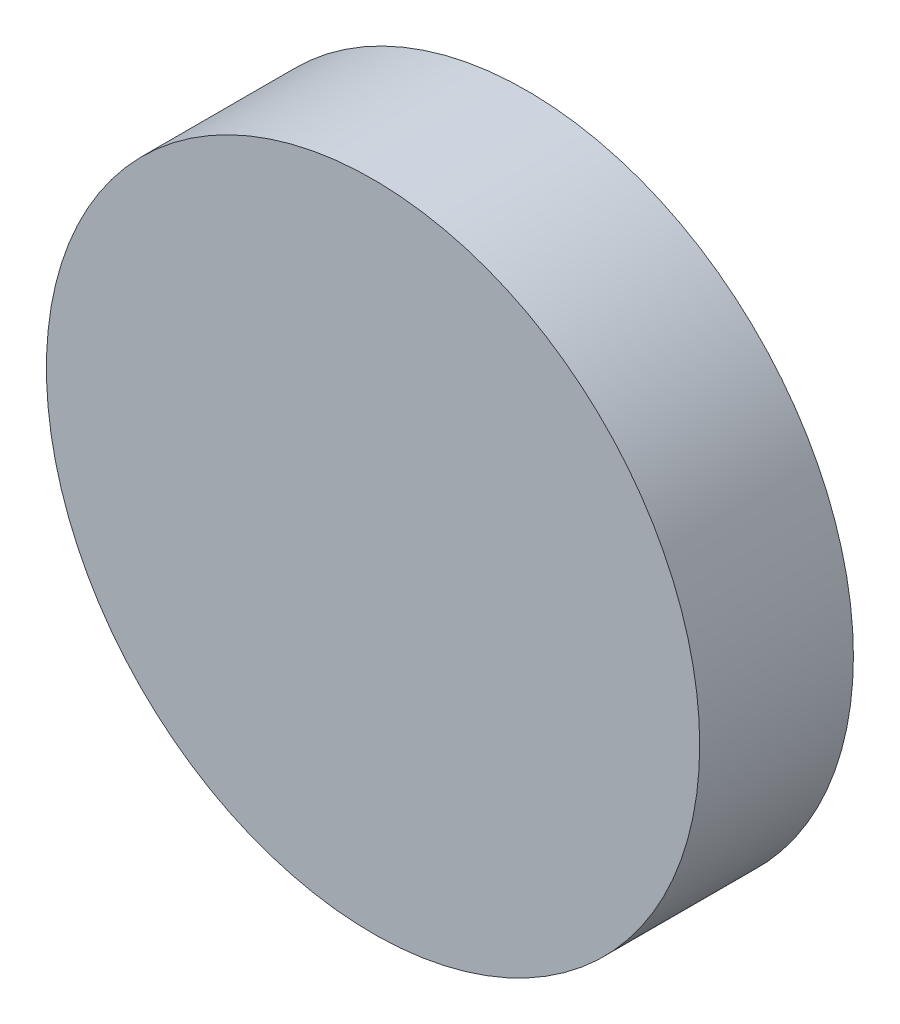
SolidWorks part; units mm, degrees
ref_plane "Front Plane" through (0, 0, 0) normal (0, 0, 1) x (1, 0, 0)
ref_plane "Top Plane" through (0, 0, 0) normal (0, 1, 0) x (1, 0, 0)
ref_plane "Right Plane" through (0, 0, 0) normal (1, 0, 0) x (0, 0, -1)
sketch "Sketch1" plane through (0, 0, 0) normal (0, 0, 1) x (1, 0, 0)
  circle A0 centre (0, 0) radius 4.25
  dimension "D1" = 8.5
extrude "Boss-Extrude1" add sketch "Sketch1" along normal blind 2
